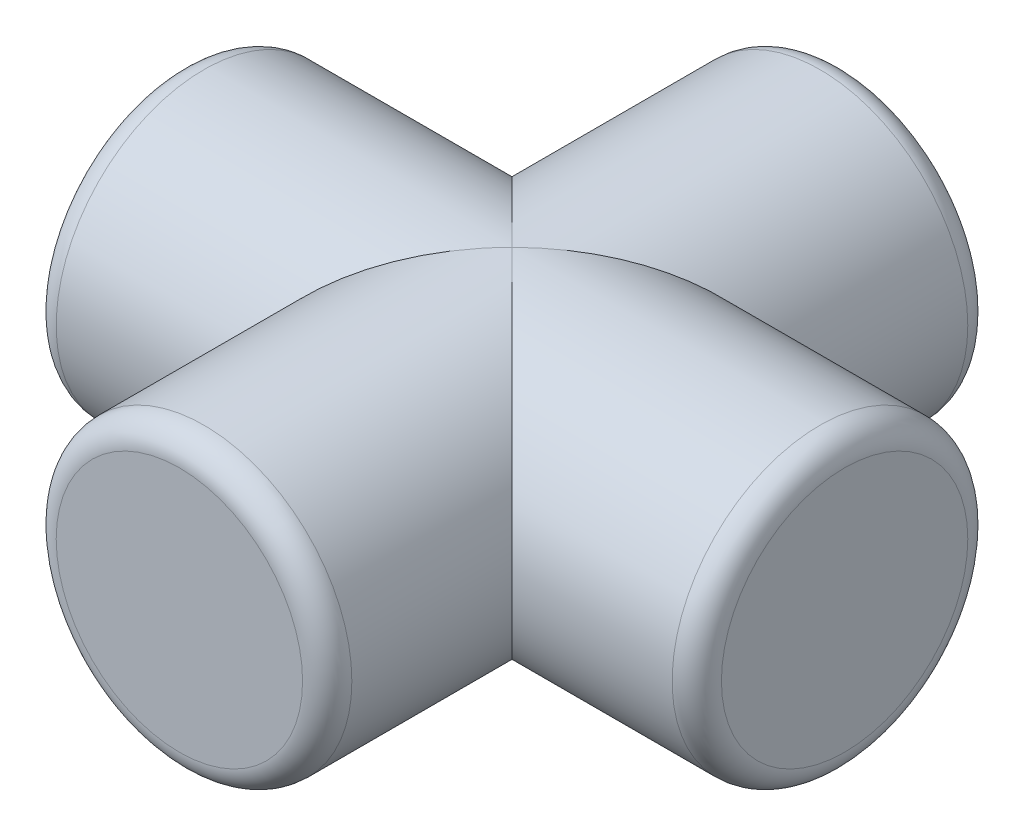
SolidWorks part; units mm, degrees
material "Cast Carbon Steel"
ref_plane "Front Plane" through (0, 0, 0) normal (0, 0, 1) x (1, 0, 0)
ref_plane "Top Plane" through (0, 0, 0) normal (0, 1, 0) x (1, 0, 0)
ref_plane "Right Plane" through (0, 0, 0) normal (1, 0, 0) x (0, 0, -1)
sketch "Sketch2" plane through (0, 0, 0) normal (0, 0, 1) x (1, 0, 0)
  circle A0 centre (0, 0) radius 7.62
extrude "Boss-Extrude1" add sketch "Sketch2" along normal blind 34.29
sketch "Sketch3" plane through (0, 0, 0) normal (1, 0, 0) x (0, 0, -1)
  circle A0 centre (-17.145, 0) radius 7.62
extrude "Boss-Extrude2" add sketch "Sketch3" along normal blind 17.145 and the other way blind 17.145
fillet "Fillet1" radius 1.27 4 edges at (7.62, 0, 34.29) (17.145, 0, 9.525) (-17.145, 0, 9.525) (7.62, 0, 0)
scale "Scale1" scale about centroid uniform scaling yes scale factor 2
